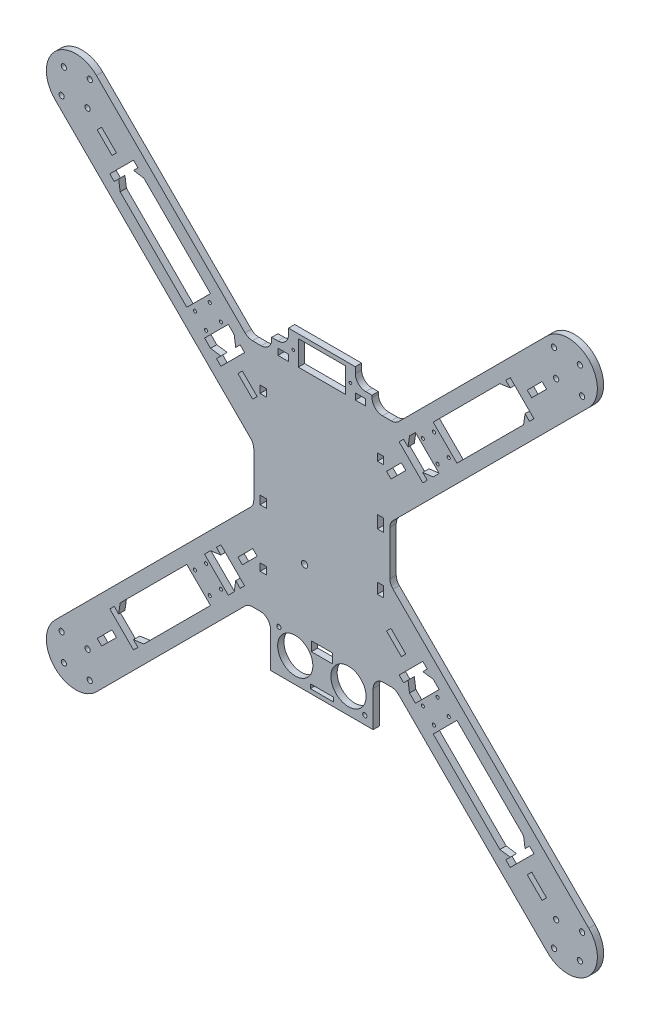
SolidWorks part; units mm, degrees
material "Custom Plastic"
ref_plane "Front Plane" through (0, 0, 0) normal (0, 0, 1) x (1, 0, 0)
ref_plane "Top Plane" through (0, 0, 0) normal (0, 1, 0) x (1, 0, 0)
ref_plane "Right Plane" through (0, 0, 0) normal (1, 0, 0) x (0, 0, -1)
sketch "Sketch1" plane through (0, 0, 0) normal (0, 0, 1) x (1, 0, 0)
  line L0 (117.5, 117.5) -> (-117.5, 117.5) construction
  line L1 (-117.5, 117.5) -> (117.5, -117.5) construction
  line L2 (117.5, -117.5) -> (-117.5, -117.5) construction
  line L3 (-117.5, -117.5) -> (117.5, 117.5) construction
  line L4 (117.5, 117.5) -> (117.5, -117.5) construction
  line L5 (-117.5, 117.5) -> (-117.5, -117.5) construction
  line L6 (0, 117.5) -> (0, -117.5) construction
  line L7 (35.201, 55) -> (15.95, 55)
  line L8 (-32.5, 55) -> (32.5, 55) construction
  line L9 (-35.201, 55) -> (-107.6005, 127.3995)
  line L10 (-127.3995, 107.6005) -> (-32.5, 12.701)
  line L11 (-117.5, 0) -> (117.5, 0) construction
  line L12 (-32.5, 12.701) -> (-32.5, -12.701)
  line L13 (32.5, 55) -> (32.5, -55) construction
  line L14 (32.5, -55) -> (-32.5, -55) construction
  line L15 (-32.5, -55) -> (-32.5, 55) construction
  line L16 (32.5, 55) -> (-32.5, -55) construction
  line L17 (-24.5, -55) -> (-24.5, -77)
  line L18 (-127.3995, -107.6005) -> (-32.5, -12.701)
  line L19 (-24.5, -77) -> (24.5, -77)
  line L20 (-35.201, -55) -> (-107.6005, -127.3995)
  line L21 (35.201, -55) -> (24.5, -55)
  line L22 (35.201, -55) -> (107.6005, -127.3995)
  line L23 (127.3995, -107.6005) -> (32.5, -12.701)
  line L24 (32.5, 12.701) -> (32.5, -12.701)
  line L25 (127.3995, 107.6005) -> (32.5, 12.701)
  line L26 (35.201, 55) -> (107.6005, 127.3995)
  line L27 (24.5, -55) -> (24.5, -77)
  line L28 (-24.5, -55) -> (-35.201, -55)
  line L29 (-15.95, 55) -> (-15.95, 68.8)
  line L30 (-15.95, 68.8) -> (15.95, 68.8)
  line L31 (15.95, 55) -> (15.95, 68.8)
  line L32 (-15.95, 55) -> (-35.201, 55)
  arc A0 (-107.6005, 127.3995) -> (-127.3995, 107.6005) centre (-117.5, 117.5) ccw
  arc A12 (-107.6005, -127.3995) -> (-127.3995, -107.6005) centre (-117.5, -117.5) cw
  arc A16 (107.6005, -127.3995) -> (127.3995, -107.6005) centre (117.5, -117.5) ccw
  arc A24 (107.6005, 127.3995) -> (127.3995, 107.6005) centre (117.5, 117.5) cw
  point P3 (0, 0)
  point P18 (0, 0)
  point P21 (0, -77)
  point P26 (0, 68.8)
  point P33 (-117.5, 117.5)
  point P34 (-32.5, 0)
  point P65 (0, -55)
  point P80 (0, 55)
  dimension "D3" = 14
  dimension "D8" = 24.5
  dimension "D7" = 22
  dimension "D1" = 235
  dimension "D2" = 235
  dimension "D4" = 65
  dimension "D5" = 110
  dimension "D6" = 28
  dimension "D9" = 13.8
  dimension "D10" = 31.9
extrude "Boss-Extrude1" add sketch "Sketch1" against normal blind 3
sketch "Sketch4" plane through (0, 0, 0) normal (0, 0, 1) x (1, 0, 0)
  line L0 (0, 0) -> (0, 55) construction
  line L2 (0, 0) -> (-32.5, 0) construction
  line L3 (-32.5, 12.701) -> (-32.5, -12.701) construction
  line L4 (-32.5, 0) -> (-32.5, 12.701) construction
  line L5 (-32.5, 12.701) -> (-127.3995, 107.6005) construction
  line L6 (-35.201, 55) -> (-107.6005, 127.3995) construction
  line L7 (-107.6005, 127.3995) -> (-127.3995, 107.6005) construction
  line L8 (-110.7825, 124.2175) -> (-124.2175, 110.7825) construction
  line L9 (-123.1569, 123.1569) -> (-111.8431, 111.8431) construction
  circle A20 centre (-110.7825, 124.2175) radius 1.25
  circle A21 centre (-124.2175, 110.7825) radius 1.25
  circle A22 centre (-123.1569, 123.1569) radius 1.25
  circle A23 centre (-111.8431, 111.8431) radius 1.25
  circle A24 centre (111.8431, 111.8431) radius 1.25
  circle A25 centre (110.7825, 124.2175) radius 1.25
  circle A26 centre (123.1569, 123.1569) radius 1.25
  circle A27 centre (124.2175, 110.7825) radius 1.25
  circle A28 centre (111.8431, -111.8431) radius 1.25
  circle A29 centre (124.2175, -110.7825) radius 1.25
  circle A30 centre (123.1569, -123.1569) radius 1.25
  circle A31 centre (110.7825, -124.2175) radius 1.25
  circle A32 centre (-111.8431, -111.8431) radius 1.25
  circle A33 centre (-110.7825, -124.2175) radius 1.25
  circle A34 centre (-123.1569, -123.1569) radius 1.25
  circle A35 centre (-124.2175, -110.7825) radius 1.25
  point P16 (-117.5, 117.5)
  point P19 (-117.5, 117.5)
  point P26 (-117.5, 117.5)
  point P62 (0, 0)
  dimension "D1" = 55
  dimension "D4" = 2.5
  dimension "D2" = 19
  dimension "D5" = 35.201
  dimension "D3" = 16
extrude "Cut-Extrude1" cut sketch "Sketch4" against normal blind 4.5
sketch "Sketch5" plane through (0, 0, 0) normal (0, 0, 1) x (1, 0, 0)
  line L4 (0, 0) -> (0, 14.0392) construction
  line L6 (15.95, 68.8) -> (-15.95, 68.8) construction
  line L7 (-11.25, 66.8) -> (-11.25, 55)
  line L8 (-11.25, 55) -> (11.25, 55)
  line L9 (11.25, 55) -> (11.25, 66.8)
  line L10 (11.25, 66.8) -> (-11.25, 66.8)
  line L12 (0, 66.8) -> (0, 55) construction
  line L13 (-13.65, 60.9) -> (13.65, 60.9) construction
  circle A2 centre (-13.65, 60.9) radius 0.65
  circle A3 centre (13.65, 60.9) radius 0.65
  point P20 (0, 60.9)
  point P21 (0, 60.9)
  dimension "D8" = 1.3
  dimension "D9" = 1.3
  dimension "D2" = 2
  dimension "D10" = 27.3
  dimension "D11" = 22.5
  dimension "D12" = 11.8
extrude "Cut-Extrude2" cut sketch "Sketch5" against normal blind 4.5
sketch "Sketch6" plane through (0, 0, 0) normal (0, 0, 1) x (1, 0, 0)
  line L1 (-11.25, 55) -> (11.25, 55) construction
  circle A0 centre (-8.25, -25) radius 1.5
  dimension "D3" = 3
  dimension "D1" = 80
  dimension "D2" = 3
extrude "Cut-Extrude3" cut sketch "Sketch6" against normal blind 4.5
sketch "Sketch7" plane through (0, 0, 0) normal (0, 0, 1) x (1, 0, 0)
  line L0 (-22.5, -55) -> (-22.5, -75) construction
  line L5 (-22.5, -75) -> (22.5, -75) construction
  line L6 (22.5, -75) -> (22.5, -55) construction
  line L7 (22.5, -55) -> (-22.5, -55) construction
  line L8 (0, -55) -> (0, -75) construction
  line L9 (-12.7, -65) -> (0, -65) construction
  line L10 (-24.5, -77) -> (24.5, -77) construction
  line L11 (-24.5, -55) -> (-24.5, -77) construction
  line L12 (-5, -55) -> (-5, -59.5)
  line L13 (-5, -59.5) -> (5, -59.5)
  line L15 (5, -55) -> (-5, -55)
  line L16 (-5.5, -75) -> (-5.5, -73)
  line L17 (-5.5, -73) -> (5.5, -73)
  line L21 (5.5, -75) -> (-5.5, -75)
  line L22 (5, -55) -> (5, -59.5)
  line L23 (5.5, -75) -> (5.5, -73)
  circle A5 centre (-20.5, -57) radius 1
  circle A6 centre (-12.7, -65) radius 8.4
  circle A7 centre (12.7, -65) radius 8.4
  circle A8 centre (20.5, -73) radius 1
  point P25 (0, -59.5)
  point P26 (0, -73)
  dimension "D3" = 2
  dimension "D6" = 20
  dimension "D13" = 5.5
  dimension "D5" = 45
  dimension "D1" = 2
  dimension "D4" = 16.8
  dimension "D14" = 2
  dimension "D2" = 2
  dimension "D7" = 2
  dimension "D8" = 2
  dimension "D9" = 12.7
  dimension "D10" = 5
  dimension "D11" = 4.5
  dimension "D12" = 2
  dimension "D15" = 2
  dimension "D16" = 2
extrude "Cut-Extrude4" cut sketch "Sketch7" against normal blind 4.5
sketch "Sketch8" plane through (0, 0, 0) normal (0, 0, 1) x (1, 0, 0)
  line L0 (101.2365, -89.9228) -> (89.9228, -101.2365)
  line L1 (89.9228, -101.2365) -> (87.8015, -99.1152)
  line L2 (36.8898, -48.2035) -> (48.2035, -36.8898)
  line L3 (48.2035, -36.8898) -> (50.3249, -39.0111)
  line L4 (105.4792, -85.6802) -> (85.6802, -105.4792) construction
  line L5 (127.3995, -107.6005) -> (32.5, -12.701) construction
  line L6 (35.201, -55) -> (107.6005, -127.3995) construction
  line L7 (40.0718, -37.9505) -> (37.9505, -40.0718)
  line L8 (115.8431, -107.8431) -> (111.8431, -111.8431) construction
  line L9 (37.9505, -40.0718) -> (30.8794, -33.0007)
  line L10 (50.3249, 39.0111) -> (48.2035, 36.8898)
  line L11 (30.8794, -33.0007) -> (33.0007, -30.8794)
  line L12 (33.0007, -30.8794) -> (40.0718, -37.9505)
  line L13 (42.5467, -42.5467) -> (39.0111, -39.0111) construction
  line L14 (35.201, -55) -> (107.6005, -127.3995) construction
  line L15 (100.1759, -98.0546) -> (98.0546, -100.1759)
  line L16 (98.0546, -100.1759) -> (105.1256, -107.247)
  line L17 (105.1256, -107.247) -> (107.247, -105.1256)
  line L18 (107.247, -105.1256) -> (100.1759, -98.0546)
  line L19 (99.1152, -99.1152) -> (95.5797, -95.5797) construction
  line L20 (-101.2365, -89.9228) -> (-99.1152, -87.8015)
  line L21 (-100.1759, -98.0546) -> (-107.247, -105.1256)
  line L22 (-107.247, -105.1256) -> (-105.1256, -107.247)
  line L23 (-105.1256, -107.247) -> (-98.0546, -100.1759)
  line L24 (-98.0546, -100.1759) -> (-100.1759, -98.0546)
  line L25 (-89.9228, -101.2365) -> (-101.2365, -89.9228)
  line L26 (-36.8898, -48.2035) -> (-39.0111, -50.3249)
  line L27 (-48.2035, -36.8898) -> (-36.8898, -48.2035)
  line L28 (-37.9505, -40.0718) -> (-40.0718, -37.9505)
  line L29 (-30.8794, -33.0007) -> (-37.9505, -40.0718)
  line L30 (-40.0718, -37.9505) -> (-33.0007, -30.8794)
  line L31 (-33.0007, -30.8794) -> (-30.8794, -33.0007)
  line L32 (-89.9228, 101.2365) -> (-87.8015, 99.1152)
  line L33 (-98.0546, 100.1759) -> (-105.1256, 107.247)
  line L34 (-105.1256, 107.247) -> (-107.247, 105.1256)
  line L35 (-107.247, 105.1256) -> (-100.1759, 98.0546)
  line L36 (-100.1759, 98.0546) -> (-98.0546, 100.1759)
  line L37 (-101.2365, 89.9228) -> (-89.9228, 101.2365)
  line L38 (-48.2035, 36.8898) -> (-50.3249, 39.0111)
  line L39 (-36.8898, 48.2035) -> (-48.2035, 36.8898)
  line L40 (-40.0718, 37.9505) -> (-37.9505, 40.0718)
  line L41 (-33.0007, 30.8794) -> (-40.0718, 37.9505)
  line L42 (-37.9505, 40.0718) -> (-30.8794, 33.0007)
  line L43 (-30.8794, 33.0007) -> (-33.0007, 30.8794)
  line L44 (101.2365, 89.9228) -> (99.1152, 87.8015)
  line L45 (100.1759, 98.0546) -> (107.247, 105.1256)
  line L46 (107.247, 105.1256) -> (105.1256, 107.247)
  line L47 (105.1256, 107.247) -> (98.0546, 100.1759)
  line L48 (98.0546, 100.1759) -> (100.1759, 98.0546)
  line L49 (89.9228, 101.2365) -> (101.2365, 89.9228)
  line L50 (36.8898, 48.2035) -> (39.0111, 50.3249)
  line L51 (48.2035, 36.8898) -> (36.8898, 48.2035)
  line L52 (37.9505, 40.0718) -> (40.0718, 37.9505)
  line L53 (30.8794, 33.0007) -> (37.9505, 40.0718)
  line L54 (40.0718, 37.9505) -> (33.0007, 30.8794)
  line L55 (33.0007, 30.8794) -> (30.8794, 33.0007)
  line L56 (32.5, 12.701) -> (127.3995, 107.6005) construction
  line L57 (41.8396, 53.1533) -> (84.9731, 96.2868)
  line L58 (96.2868, 84.9731) -> (53.1533, 41.8396)
  line L59 (87.8015, 99.1152) -> (89.9228, 101.2365)
  line L60 (99.1152, -87.8015) -> (96.9939, -89.9228)
  line L61 (-96.2868, -84.9731) -> (-53.1533, -41.8396)
  line L62 (96.9939, -89.9228) -> (96.2868, -84.9731)
  line L63 (99.1152, -87.8015) -> (101.2365, -89.9228)
  line L64 (87.8015, -99.1152) -> (89.9228, -96.9939)
  line L65 (-87.8015, -99.1152) -> (-89.9228, -101.2365)
  line L66 (89.9228, -96.9939) -> (84.9731, -96.2868)
  line L67 (84.9731, -96.2868) -> (41.8396, -53.1533)
  line L68 (50.3249, -39.0111) -> (48.2035, -41.1325)
  line L69 (48.2035, -41.1325) -> (53.1533, -41.8396)
  line L70 (53.1533, -41.8396) -> (96.2868, -84.9731)
  line L71 (39.0111, -50.3249) -> (41.1325, -48.2035)
  line L72 (41.1325, -48.2035) -> (41.8396, -53.1533)
  line L73 (39.0111, -50.3249) -> (36.8898, -48.2035)
  line L74 (-89.9228, -96.9939) -> (-84.9731, -96.2868)
  line L75 (-87.8015, -99.1152) -> (-89.9228, -96.9939)
  line L76 (-96.9939, -89.9228) -> (-96.2868, -84.9731)
  line L77 (-99.1152, -87.8015) -> (-96.9939, -89.9228)
  line L78 (-41.1325, -48.2035) -> (-41.8396, -53.1533)
  line L79 (-39.0111, -50.3249) -> (-41.1325, -48.2035)
  line L80 (-48.2035, -41.1325) -> (-53.1533, -41.8396)
  line L81 (-50.3249, -39.0111) -> (-48.2035, -41.1325)
  line L82 (-96.9939, 89.9228) -> (-96.2868, 84.9731)
  line L83 (-99.1152, 87.8015) -> (-96.9939, 89.9228)
  line L84 (-89.9228, 96.9939) -> (-84.9731, 96.2868)
  line L85 (-87.8015, 99.1152) -> (-89.9228, 96.9939)
  line L86 (-48.2035, 41.1325) -> (-53.1533, 41.8396)
  line L87 (-50.3249, 39.0111) -> (-48.2035, 41.1325)
  line L88 (-41.1325, 48.2035) -> (-41.8396, 53.1533)
  line L89 (-39.0111, 50.3249) -> (-41.1325, 48.2035)
  line L90 (89.9228, 96.9939) -> (84.9731, 96.2868)
  line L91 (87.8015, 99.1152) -> (89.9228, 96.9939)
  line L92 (96.9939, 89.9228) -> (96.2868, 84.9731)
  line L93 (99.1152, 87.8015) -> (96.9939, 89.9228)
  line L94 (41.1325, 48.2035) -> (41.8396, 53.1533)
  line L95 (39.0111, 50.3249) -> (41.1325, 48.2035)
  line L96 (48.1429, 41.1931) -> (53.1533, 41.8396)
  line L97 (50.3249, 39.0111) -> (48.1429, 41.1931)
  line L98 (-39.0111, 50.3249) -> (-36.8898, 48.2035)
  line L99 (-53.1533, 41.8396) -> (-96.2868, 84.9731)
  line L100 (-99.1152, 87.8015) -> (-101.2365, 89.9228)
  line L101 (-84.9731, 96.2868) -> (-41.8396, 53.1533)
  line L102 (-41.8396, -53.1533) -> (-84.9731, -96.2868)
  line L103 (-50.3249, -39.0111) -> (-48.2035, -36.8898)
  line L104 (96.2868, 84.9731) -> (84.9731, 96.2868) construction
  line L105 (53.1533, 41.8396) -> (41.8396, 53.1533) construction
  point P10 (95.5797, -95.5797)
  point P11 (95.5797, -95.5797)
  point P18 (-49.2642, 40.0718)
  point P19 (-49.2642, -40.0718)
  point P68 (0, 0)
  point P122 (0, 0)
  dimension "D1" = 23
  dimension "D2" = 75
  dimension "D3" = 3
  dimension "D4" = 10
  dimension "D5" = 5
  dimension "D6" = 6
  dimension "D7" = 3
  dimension "D8" = 10
  dimension "D9" = 5
  dimension "D11" = 6
  dimension "D12" = 3
  dimension "D13" = 4
  dimension "D14" = 3
  dimension "D15" = 3
  dimension "D16" = 4
  dimension "D17" = 3
  dimension "D18" = 3
  dimension "D19" = 4
  dimension "D20" = 3
  dimension "D21" = 3
  dimension "D22" = 4
  dimension "D23" = 3
  dimension "D24" = 3
  dimension "D25" = 4
  dimension "D26" = 3
  dimension "D27" = 4
  dimension "D28" = 3
  dimension "D29" = 3
  dimension "D30" = 4
  dimension "D31" = 4
  dimension "D32" = 3
  dimension "D33" = 3
  dimension "D34" = 4
  dimension "D35" = 4
  dimension "D36" = 3
  dimension "D37" = 3
  dimension "D38" = 4
  dimension "D39" = 4
  dimension "D40" = 3
  dimension "D41" = 3
  dimension "D42" = 4
  dimension "D43" = 4
  dimension "D10" = 4
extrude "Cut-Extrude5" cut sketch "Sketch8" against normal through all
sketch "Sketch9" plane through (-5.6569, 5.6569, 0) normal (0.7071, -0.7071, 0) x (0, 0, -1)
  line L0 (3, 128.1701) -> (3, 67.1701) construction
  line L1 (3, 83.1701) -> (0, 83.1701)
  line L2 (3, 83.1701) -> (3, 71.1701)
  line L3 (3, 71.1701) -> (0, 71.1701)
  line L4 (0, 83.1701) -> (0, 71.1701)
  line L5 (0, 128.1701) -> (0, 67.1701) construction
  line L6 (0, 0) -> (28.0274, 0) construction
  line L7 (3, 63.1701) -> (0, 63.1701) construction
  dimension "D1" = 8
  dimension "D2" = 12
extrude "Boss-Extrude2" add sketch "Sketch9" along normal up to next
sketch "Sketch11" plane through (5.6569, 5.6569, 0) normal (-0.7071, -0.7071, 0) x (0, 0, 1)
  line L0 (-3, -128.1701) -> (-3, -67.1701) construction
  line L1 (-3, -71.1701) -> (0, -71.1701)
  line L2 (-3, -71.1701) -> (-3, -83.1701)
  line L3 (-3, -83.1701) -> (0, -83.1701)
  line L4 (0, -71.1701) -> (0, -83.1701)
  line L5 (0, -128.1701) -> (0, -67.1701) construction
  line L6 (-3, -63.1701) -> (0, -63.1701) construction
  dimension "D1" = 8
  dimension "D2" = 12
extrude "Boss-Extrude3" add sketch "Sketch11" along normal up to next
sketch "Sketch12" plane through (5.6569, -5.6569, 0) normal (-0.7071, 0.7071, 0) x (0, 0, 1)
  line L0 (-3, -128.1701) -> (-3, -67.1701) construction
  line L1 (-3, -71.1701) -> (0, -71.1701)
  line L2 (-3, -71.1701) -> (-3, -83.1701)
  line L3 (-3, -83.1701) -> (0, -83.1701)
  line L4 (0, -71.1701) -> (0, -83.1701)
  line L5 (0, -128.1701) -> (0, -67.1701) construction
  dimension "D1" = 8
  dimension "D2" = 12
extrude "Boss-Extrude4" add sketch "Sketch12" along normal up to next
sketch "Sketch13" plane through (5.6569, 5.6569, 0) normal (-0.7071, -0.7071, 0) x (0, 0, 1)
  line L0 (-3, 67.1701) -> (-3, 128.1701) construction
  line L1 (-3, 71.1701) -> (0, 71.1701)
  line L2 (-3, 71.1701) -> (-3, 83.1701)
  line L3 (-3, 83.1701) -> (0, 83.1701)
  line L4 (0, 71.1701) -> (0, 83.1701)
  line L5 (0, 67.1701) -> (0, 128.1701) construction
  dimension "D1" = 8
  dimension "D2" = 12
extrude "Boss-Extrude5" add sketch "Sketch13" along normal up to next
sketch "Sketch14" plane through (0, 0, -3) normal (0, 0, -1) x (-1, 0, 0)
  line L0 (32.5, 0) -> (-32.5, 0) construction
  line L1 (32.5, 12.701) -> (32.5, -12.701) construction
  line L2 (-32.5, -12.701) -> (-32.5, 12.701) construction
  line L3 (28, -38.5) -> (28, 38.5) construction
  line L14 (-26.5, 13) -> (-26.5, 7)
  line L17 (-26.5, 7) -> (-29.5, 7)
  line L19 (-26.5, 13) -> (-29.5, 13)
  line L23 (26.5, -38.5) -> (29.5, -38.5)
  line L24 (26.5, -38.5) -> (26.5, -35)
  line L25 (26.5, -35) -> (29.5, -35)
  line L26 (29.5, -38.5) -> (29.5, -35)
  line L27 (26.5, -11) -> (29.5, -11)
  line L28 (26.5, -11) -> (26.5, -7)
  line L29 (26.5, -7) -> (29.5, -7)
  line L30 (29.5, -11) -> (29.5, -7)
  line L31 (26.5, 35) -> (29.5, 35)
  line L32 (26.5, 35) -> (26.5, 38.5)
  line L33 (26.5, 38.5) -> (29.5, 38.5)
  line L34 (29.5, 35) -> (29.5, 38.5)
  line L35 (-29.5, 13) -> (-29.5, 7)
  line L36 (32.5, 12.701) -> (32.5, -12.701) construction
  line L37 (-26.5, -20) -> (-29.5, -20)
  line L38 (-26.5, -20) -> (-26.5, -15)
  line L39 (-26.5, -15) -> (-29.5, -15)
  line L40 (-29.5, -20) -> (-29.5, -15)
  line L41 (-26.5, 35) -> (-29.5, 35)
  line L42 (-26.5, 35) -> (-26.5, 38.5)
  line L43 (-26.5, 38.5) -> (-29.5, 38.5)
  line L44 (-29.5, 35) -> (-29.5, 38.5)
  line L45 (-32.5, -12.701) -> (-32.5, 12.701) construction
  point P11 (28, -38.5)
  point P16 (28, 0)
  point P28 (-28, 13)
  point P38 (-28, 7)
  dimension "D2" = 3
  dimension "D3" = 3.5
  dimension "D4" = 24
  dimension "D5" = 7
  dimension "D6" = 22
  dimension "D7" = 6
  dimension "D8" = 3.5
  dimension "D9" = 22
  dimension "D10" = 4
  dimension "D11" = 3.5
  dimension "D12" = 42
  dimension "D13" = 5
  dimension "D14" = 3
  dimension "D15" = 3
  dimension "D16" = 3
  dimension "D17" = 7
extrude "Cut-Extrude6" cut sketch "Sketch14" against normal through all
sketch "Sketch15" plane through (0, 0, -3) normal (0, 0, -1) x (-1, 0, 0)
  line L0 (-55.2746, -48.2035) -> (-48.2035, -55.2746) construction
  line L1 (-48.2035, -55.2746) -> (-53.5068, -60.5779) construction
  line L2 (-53.5068, -60.5779) -> (-60.5779, -53.5068) construction
  line L3 (-60.5779, -53.5068) -> (-55.2746, -48.2035) construction
  line L4 (-64.2902, -44.4912) -> (-44.4912, -64.2902) construction
  line L5 (-127.3995, -107.6005) -> (-32.5, -12.701) construction
  line L6 (-35.201, -55) -> (-107.6005, -127.3995) construction
  line L7 (-57.0424, -57.0424) -> (-51.7391, -51.7391) construction
  line L8 (-53.1533, -64.467) -> (-64.467, -53.1533) construction
  circle A6 centre (-60.5779, -53.5068) radius 0.75
  circle A7 centre (-55.2746, -48.2035) radius 0.75
  circle A8 centre (-48.2035, -55.2746) radius 0.75
  circle A9 centre (-53.5068, -60.5779) radius 0.75
  circle A10 centre (-53.5068, 60.5779) radius 0.75
  circle A11 centre (-48.2035, 55.2746) radius 0.75
  circle A12 centre (-60.5779, 53.5068) radius 0.75
  circle A13 centre (-55.2746, 48.2035) radius 0.75
  circle A14 centre (60.5779, 53.5068) radius 0.75
  circle A15 centre (55.2746, 48.2035) radius 0.75
  circle A16 centre (53.5068, 60.5779) radius 0.75
  circle A17 centre (48.2035, 55.2746) radius 0.75
  circle A18 centre (53.5068, -60.5779) radius 0.75
  circle A19 centre (48.2035, -55.2746) radius 0.75
  circle A20 centre (60.5779, -53.5068) radius 0.75
  circle A21 centre (55.2746, -48.2035) radius 0.75
  point P12 (-54.3907, -54.3907)
  point P19 (-54.3907, -54.3907)
  point P47 (0, 0)
  dimension "D3" = 1.5
  dimension "D1" = 7.5
  dimension "D2" = 10
  dimension "D4" = 2.5
  dimension "D5" = 4
extrude "Cut-Extrude7" cut sketch "Sketch15" against normal through all
sketch "Sketch17" plane through (0, 0, -3) normal (0, 0, -1) x (-1, 0, 0)
  line L0 (0, 68.8) -> (0, 41.1241) construction
  line L1 (15.95, 55) -> (23.95, 55)
  line L2 (15.95, 55) -> (15.95, 61)
  line L3 (15.95, 61) -> (23.95, 61)
  line L4 (23.95, 55) -> (23.95, 61)
  line L5 (-15.95, 68.8) -> (15.95, 68.8) construction
  line L6 (-15.95, 55) -> (-15.95, 58)
  line L7 (20.95, 55) -> (15.95, 55)
  line L10 (15.95, 55) -> (15.95, 58)
  line L11 (-20.95, 58) -> (-15.95, 58)
  line L12 (-20.95, 55) -> (-20.95, 58)
  line L13 (-20.95, 55) -> (-15.95, 55)
  line L14 (-23.95, 55) -> (-23.95, 61)
  line L15 (-15.95, 61) -> (-23.95, 61)
  line L16 (-15.95, 55) -> (-15.95, 61)
  line L17 (-15.95, 55) -> (-23.95, 55)
  dimension "D1" = 6
  dimension "D2" = 8
extrude "Boss-Extrude8" add sketch "Sketch17" against normal blind 3 contours L2 L3 L4 L1 | L16 L15 L14 L17
sketch "Sketch19" plane through (0, 0, -3) normal (0, 0, -1) x (-1, 0, 0)
  line L0 (15.95, 61) -> (23.95, 61) construction
  line L1 (20.95, 58) -> (15.95, 58)
  line L2 (20.95, 58) -> (20.95, 55)
  line L3 (20.95, 55) -> (15.95, 55)
  line L4 (15.95, 58) -> (15.95, 55)
  line L5 (23.95, 55) -> (23.95, 61) construction
  line L6 (0, 68.8) -> (0, 43.8944) construction
  line L7 (-15.95, 68.8) -> (15.95, 68.8) construction
  line L8 (-15.95, 58) -> (-15.95, 55)
  line L9 (-20.95, 55) -> (-15.95, 55)
  line L10 (-20.95, 58) -> (-20.95, 55)
  line L11 (-20.95, 58) -> (-15.95, 58)
  dimension "D1" = 5
  dimension "D2" = 3
  dimension "D3" = 3
  dimension "D4" = 3
extrude "Cut-Extrude9" cut sketch "Sketch19" against normal through all
fillet "Fillet1" radius 5 14 edges at (-32.5, -12.701, -1.5) (-32.5, 12.701, -1.5) (32.5, 12.701, -1.5) (32.5, -12.701, -1.5) (24.5, -55, -1.5) (35.201, -55, -1.5) (-24.5, -55, -1.5) (-35.201, -55, -1.5) (15.95, 61, -1.5) (23.95, 55, -1.5) (35.201, 55, -1.5) (-15.95, 61, -1.5) (-23.95, 55, -1.5) (-35.201, 55, -1.5)
